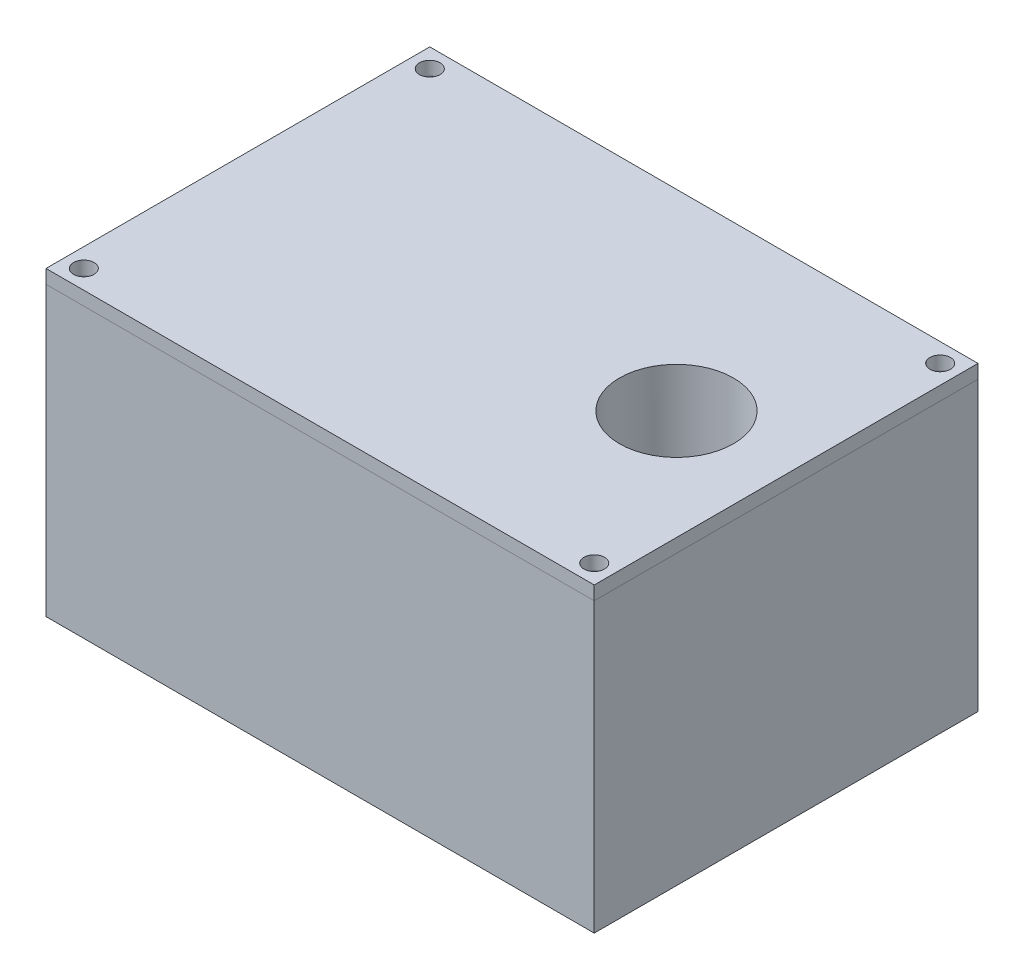
SolidWorks part; units mm, degrees
ref_plane "Front Plane" through (0, 0, 0) normal (0, 0, 1) x (1, 0, 0)
ref_plane "Top Plane" through (0, 0, 0) normal (0, 1, 0) x (1, 0, 0)
ref_plane "Right Plane" through (0, 0, 0) normal (1, 0, 0) x (0, 0, -1)
sketch "Sketch1" plane through (0, 0, 0) normal (0, 1, 0) x (1, 0, 0)
  line L1 (0, 0) -> (127, 0)
  line L2 (0, 0) -> (0, 88.9)
  line L3 (0, 88.9) -> (127, 88.9)
  line L4 (127, 0) -> (127, 88.9)
  dimension "D1" = 127
  dimension "D2" = 88.9
extrude "Boss-Extrude1" add sketch "Sketch1" along normal blind 3.175
sketch "Sketch2" plane through (0, 3.175, 0) normal (0, 1, 0) x (1, 0, 0)
  line L1 (22.225, 3.175) -> (104.775, 3.175)
  line L2 (3.175, 22.225) -> (3.175, 66.675)
  line L3 (22.225, 85.725) -> (104.775, 85.725)
  line L4 (0, 88.9) -> (0, 0)
  line L5 (0, 0) -> (127, 0)
  line L6 (127, 0) -> (127, 88.9)
  line L7 (127, 88.9) -> (0, 88.9)
  line L8 (0, 88.9) -> (0, 0)
  line L9 (0, 0) -> (127, 0)
  line L10 (127, 0) -> (127, 88.9)
  line L11 (127, 88.9) -> (0, 88.9)
  line L12 (123.825, 22.225) -> (123.825, 66.675)
  line L13 (3.175, 3.175) -> (123.825, 85.725) construction
  line L14 (3.175, 85.725) -> (123.825, 3.175) construction
  arc A0 (22.225, 3.175) -> (3.175, 22.225) centre (22.225, 22.225) cw
  arc A1 (104.775, 3.175) -> (123.825, 22.225) centre (104.775, 22.225) ccw
  arc A2 (104.775, 85.725) -> (123.825, 66.675) centre (104.775, 66.675) cw
  arc A3 (3.175, 66.675) -> (22.225, 85.725) centre (22.225, 66.675) cw
  point P2 (63.5, 44.45)
  point P6 (63.5, 88.9)
  point P8 (127, 44.45)
  point P9 (63.5, 44.45)
  dimension "D4" = 19.05
  dimension "D2" = 3.175
  dimension "D3" = 3.175
  dimension "D1" = 0
extrude "Boss-Extrude2" add sketch "Sketch2" along normal blind 63.5
extrude "Boss-Extrude3" add sketch "Sketch1<2>" along normal blind 3.175 from surface separate body starting at face at (63.5, 66.675, -44.45)
sketch "Sketch1<2>" plane through (0, 0, 0) normal (0, 1, 0) x (1, 0, 0) same geometry as "Sketch1"
sketch "Sketch3" plane through (0, 66.675, 0) normal (0, 1, 0) x (1, 0, 0)
  line L0 (63.5, 85.725) -> (63.5, 43.5575) construction
  line L1 (0, 88.9) -> (8.7546, 80.1454) construction
  line L2 (104.775, 85.725) -> (22.225, 85.725) construction
  line L3 (3.175, 44.45) -> (25.7566, 44.45) construction
  line L4 (3.175, 66.675) -> (3.175, 22.225) construction
  circle A0 centre (4.3773, 84.5227) radius 2.3812
  circle A1 centre (122.6227, 4.3773) radius 2.3812
  arc A2 (22.225, 85.725) -> (3.175, 66.675) centre (22.225, 66.675) ccw construction
  circle A3 centre (122.6227, 84.5227) radius 2.3812
  circle A4 centre (4.3773, 4.3773) radius 2.3812
  dimension "D1" = 4.7625
extrude "Cut-Extrude1" cut sketch "Sketch3" against normal blind 25.4
extrude "Cut-Extrude2" cut sketch "Sketch3<2>" against normal up to next (25.4 mm away) from surface starting at face at (63.5, 69.85, -44.45)
sketch "Sketch3<2>" plane through (0, 66.675, 0) normal (0, 1, 0) x (1, 0, 0) same geometry as "Sketch3"
sketch "Sketch4" plane through (0, 69.85, 0) normal (0, 1, 0) x (1, 0, 0)
  line L0 (127, 88.9) -> (127, 0) construction
  circle A0 centre (101.6, 44.45) radius 7.62
  point P5 (127, 44.45)
  dimension "D1" = 15.24
  dimension "D2" = 25.4
extrude "Cut-Extrude3" cut sketch "Sketch4" against normal up to next (3.175 mm away)
sketch "Sketch5" plane through (0, 0, 0) normal (-1, 0, 0) x (0, 0, 1)
  line L0 (-66.675, 3.175) -> (-22.225, 3.175) construction
  line L1 (-66.675, 3.175) -> (-22.225, 3.175) construction
  line L2 (-44.45, 3.175) -> (-44.45, 19.8438) construction
  line L3 (-50.8, 23.8125) -> (-38.1, 23.8125)
  line L4 (-50.8, 23.8125) -> (-50.8, 15.875)
  line L5 (-50.8, 15.875) -> (-38.1, 15.875)
  line L6 (-38.1, 23.8125) -> (-38.1, 15.875)
  line L7 (-50.8, 23.8125) -> (-38.1, 15.875) construction
  line L8 (-50.8, 15.875) -> (-38.1, 23.8125) construction
  point P2 (-44.45, 19.8438)
  point P8 (-44.45, 19.8438)
  dimension "D1" = 12.7
  dimension "D2" = 7.9375
  dimension "D3" = 12.7
extrude "Cut-Extrude4" cut sketch "Sketch5" against normal up to next (3.175 mm away)
fillet "Fillet1" radius 1.27 8 edges at (0, 23.8125, -44.45) (0, 19.8438, -50.8) (0, 19.8438, -38.1) (0, 15.875, -44.45) (1.5875, 15.875, -38.1) (1.5875, 23.8125, -38.1) (1.5875, 23.8125, -50.8) (1.5875, 15.875, -50.8)
sketch "Sketch6" plane through (123.825, 0, 0) normal (-1, 0, 0) x (0, 0, 1)
  line L0 (-22.225, 66.675) -> (-66.675, 66.675) construction
  line L1 (-65.405, 66.675) -> (-59.055, 66.675)
  line L2 (-65.405, 66.675) -> (-65.405, 57.15)
  line L3 (-65.405, 57.15) -> (-59.055, 57.15)
  line L4 (-59.055, 66.675) -> (-59.055, 57.15)
  line L5 (-44.45, 66.675) -> (-62.23, 66.675) construction
  line L6 (-44.45, 66.675) -> (-44.45, 52.9036) construction
  line L7 (-23.495, 57.15) -> (-29.845, 57.15)
  line L8 (-29.845, 66.675) -> (-29.845, 57.15)
  line L9 (-23.495, 66.675) -> (-29.845, 66.675)
  line L10 (-23.495, 66.675) -> (-23.495, 57.15)
  dimension "D1" = 6.35
  dimension "D2" = 9.525
  dimension "D3" = 17.78
extrude "Boss-Extrude4" add sketch "Sketch6" along normal up to next
other "Move Face1" flip direction yes face at (123.825, 61.9125, -62.23) face at (123.825, 61.9125, -26.67) face at (3.175, 61.9125, -26.67) face at (3.175, 61.9125, -62.23) offset 0.254 parameters "D1"=0.254
sketch "Sketch7" plane through (0, 0, -59.055) normal (0, 0, 1) x (1, 0, 0)
  line L0 (3.429, 57.15) -> (123.571, 57.15) construction
  line L1 (28.829, 57.15) -> (22.479, 57.15)
  line L2 (28.829, 57.15) -> (28.829, 66.675)
  line L3 (28.829, 66.675) -> (22.479, 66.675)
  line L4 (22.479, 57.15) -> (22.479, 66.675)
  line L5 (3.429, 66.675) -> (123.571, 66.675) construction
  dimension "D1" = 6.35
  dimension "D2" = 19.05
extrude "Boss-Extrude5" add sketch "Sketch7" along normal up to next
sketch "Sketch8" plane through (0, 66.675, 0) normal (0, -1, 0) x (1, 0, 0)
  line L0 (3.429, -59.055) -> (22.479, -59.055) construction
  line L1 (86.995, -29.845) -> (116.205, -29.845)
  line L2 (86.995, -29.845) -> (86.995, -59.055)
  line L3 (86.995, -59.055) -> (116.205, -59.055)
  line L4 (116.205, -29.845) -> (116.205, -59.055)
  line L5 (86.995, -29.845) -> (116.205, -59.055) construction
  line L6 (86.995, -59.055) -> (116.205, -29.845) construction
  point P0 (101.6, -44.45)
  point P1 (101.6, -44.45)
extrude "Boss-Extrude6" add sketch "Sketch8" along normal blind 44.45 from surface starting at face at (101.6, 69.85, -36.83)
extrude "Cut-Extrude5" cut sketch "Sketch4<3>" against normal up to next (44.45 mm away)
sketch "Sketch4<3>" plane through (0, 69.85, 0) normal (0, 1, 0) x (1, 0, 0) same geometry as "Sketch4"
sketch "Sketch9" plane through (0, 69.85, 0) normal (0, 1, 0) x (1, 0, 0)
  circle A0 centre (101.6, 44.45) radius 12.7
  dimension "D1" = 25.4
extrude "Cut-Extrude6" cut sketch "Sketch9" against normal blind 41.275
other "Move Face2" flip direction yes face at (101.6, 28.575, -31.75) offset 0.508 parameters "D1"=0.508
other "Move Face3" flip direction yes face at (101.6, 28.575, -31.242) offset 0.508 parameters "D1"=0.508
sketch "Sketch10" plane through (0, 57.15, 0) normal (0, -1, 0) x (1, 0, 0)
  line L16 (22.479, -59.055) -> (3.429, -59.055)
  line L17 (3.429, -59.055) -> (3.429, -65.405)
  line L18 (3.429, -65.405) -> (123.571, -65.405)
  line L19 (123.571, -65.405) -> (123.571, -59.055)
  line L20 (123.571, -59.055) -> (116.205, -59.055)
  line L21 (116.205, -59.055) -> (86.995, -59.055)
  line L22 (86.995, -59.055) -> (28.829, -59.055)
  line L23 (28.829, -59.055) -> (28.829, -29.845)
  line L24 (28.829, -29.845) -> (86.995, -29.845)
  line L25 (86.995, -29.845) -> (116.205, -29.845)
  line L26 (116.205, -29.845) -> (123.571, -29.845)
  line L27 (123.571, -29.845) -> (123.571, -23.495)
  line L28 (123.571, -23.495) -> (3.429, -23.495)
  line L29 (3.429, -23.495) -> (3.429, -29.845)
  line L30 (3.429, -29.845) -> (22.479, -29.845)
  line L31 (22.479, -29.845) -> (22.479, -59.055)
  line L32 (22.479, -59.055) -> (3.429, -59.055)
  line L33 (3.429, -59.055) -> (3.429, -65.405)
  line L34 (3.429, -65.405) -> (123.571, -65.405)
  line L35 (123.571, -65.405) -> (123.571, -59.055)
  line L36 (123.571, -59.055) -> (116.205, -59.055)
  line L37 (116.205, -59.055) -> (86.995, -59.055)
  line L38 (86.995, -59.055) -> (28.829, -59.055)
  line L39 (28.829, -59.055) -> (28.829, -29.845)
  line L40 (28.829, -29.845) -> (86.995, -29.845)
  line L41 (86.995, -29.845) -> (116.205, -29.845)
  line L42 (116.205, -29.845) -> (123.571, -29.845)
  line L43 (123.571, -29.845) -> (123.571, -23.495)
  line L44 (123.571, -23.495) -> (3.429, -23.495)
  line L45 (3.429, -23.495) -> (3.429, -29.845)
  line L46 (3.429, -29.845) -> (22.479, -29.845)
  line L47 (22.479, -29.845) -> (22.479, -59.055)
  dimension "D1" = 0
extrude "Cut-Extrude7" cut sketch "Sketch10" against normal up to surface (9.525 mm away) up to face at (63.5, 66.675, -44.45)
sketch "Sketch11" plane through (0, 66.675, 0) normal (0, -1, 0) x (1, 0, 0)
  line L0 (123.825, -22.225) -> (123.825, -66.675) construction
  line L1 (22.225, -3.175) -> (104.775, -3.175) construction
  line L2 (3.175, -66.675) -> (3.175, -22.225) construction
  line L3 (104.775, -85.725) -> (22.225, -85.725) construction
  line L12 (123.825, -22.225) -> (123.825, -66.675)
  line L13 (22.225, -3.175) -> (104.775, -3.175)
  line L14 (3.175, -66.675) -> (3.175, -22.225)
  line L15 (104.775, -85.725) -> (22.225, -85.725)
  line L16 (22.225, -6.35) -> (104.775, -6.35)
  line L17 (120.65, -22.225) -> (120.65, -66.675)
  line L18 (6.35, -66.675) -> (6.35, -22.225)
  line L19 (104.775, -82.55) -> (22.225, -82.55)
  line L20 (6.35, -44.45) -> (3.175, -44.45) construction
  arc A0 (104.775, -85.725) -> (123.825, -66.675) centre (104.775, -66.675) ccw construction
  arc A1 (123.825, -22.225) -> (104.775, -3.175) centre (104.775, -22.225) ccw construction
  arc A2 (22.225, -3.175) -> (3.175, -22.225) centre (22.225, -22.225) ccw construction
  arc A3 (3.175, -66.675) -> (22.225, -85.725) centre (22.225, -66.675) ccw construction
  arc A4 (104.775, -85.725) -> (123.825, -66.675) centre (104.775, -66.675) ccw
  arc A5 (123.825, -22.225) -> (104.775, -3.175) centre (104.775, -22.225) ccw
  arc A6 (22.225, -3.175) -> (3.175, -22.225) centre (22.225, -22.225) ccw
  arc A7 (3.175, -66.675) -> (22.225, -85.725) centre (22.225, -66.675) ccw
  arc A8 (6.35, -66.675) -> (22.225, -82.55) centre (22.225, -66.675) ccw
  arc A9 (120.65, -22.225) -> (104.775, -6.35) centre (104.775, -22.225) ccw
  arc A10 (104.775, -82.55) -> (120.65, -66.675) centre (104.775, -66.675) ccw
  arc A11 (22.225, -6.35) -> (6.35, -22.225) centre (22.225, -22.225) ccw
  point P4 (63.5, -44.45)
  point P9 (63.5, -85.725)
  point P11 (123.825, -44.45)
  point P29 (0, 0)
  point P32 (0, 0)
  point P33 (0, 0)
  dimension "D1" = 3.175
  dimension "D2" = 3.175
extrude "Boss-Extrude7" add sketch "Sketch11" along normal blind 6.35
fillet "Fillet3" [suppressed] radius 2.54
fillet "Fillet4" radius 12.7 4 edges at (116.205, 46.0375, -29.845) (116.205, 46.0375, -59.055) (86.995, 46.0375, -59.055) (86.995, 46.0375, -29.845)
fillet "Fillet5" radius 3.175 16 edges at (116.0003, 66.675, -77.9003) (63.5, 66.675, -82.55) (10.9997, 66.675, -77.9003) (6.35, 66.675, -44.45) (10.9997, 66.675, -10.9997) (63.5, 66.675, -6.35) (116.0003, 66.675, -10.9997) (86.995, 66.675, -44.45) (90.7147, 66.675, -55.3353) (101.6, 66.675, -59.055) (112.4853, 66.675, -55.3353) (116.205, 66.675, -44.45) (112.4853, 66.675, -33.5647) (101.6, 66.675, -29.845) (120.65, 66.675, -44.45) (90.7147, 66.675, -33.5647)
other "Move Face4" flip direction yes face at (10.7273, 63.5, -10.7273) face at (3.175, 63.5, -44.45) face at (10.7273, 63.5, -78.1727) face at (63.5, 63.5, -85.725) face at (116.2727, 63.5, -78.1727) face at (123.825, 63.5, -44.45) face at (63.5, 63.5, -3.175) face at (116.2727, 63.5, -10.7273) offset 0.254 parameters "D1"=0.254
